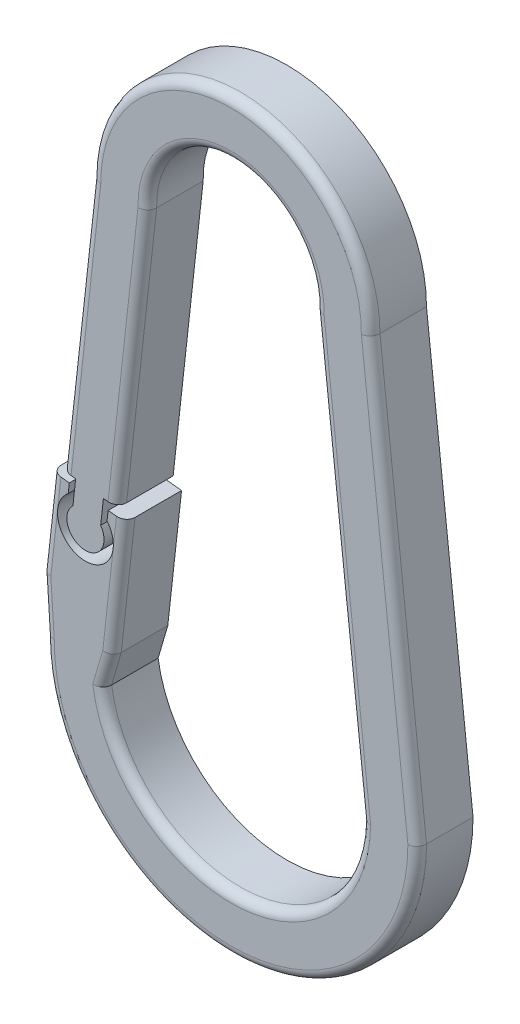
SolidWorks part; units mm, degrees
ref_plane "Спереди" through (0, 0, 0) normal (0, 0, 1) x (1, 0, 0)
ref_plane "Сверху" through (0, 0, 0) normal (0, 1, 0) x (1, 0, 0)
ref_plane "Справа" through (0, 0, 0) normal (1, 0, 0) x (0, 0, -1)
sketch "Эскиз1" plane through (0, 0, 0) normal (0, 0, 1) x (1, 0, 0)
  line L0 (-9.0941, 8.1534) -> (-7.5, 22.5)
  line L1 (10, 0) -> (7.5, 22.5)
  line L2 (0, 0) -> (0, 22.5) construction
  line L3 (6.9984, -0.1514) -> (4.4977, 22.3549)
  line L4 (-6.1124, 7.8221) -> (-4.4977, 22.3549)
  line L5 (-8.818, 6.1104) -> (-6.8302, 5.8896) construction
  line L6 (-7.0183, -0.3313) -> (-4.4977, 22.3549) construction
  line L7 (7.0183, -0.3313) -> (4.4977, 22.3549) construction
  line L8 (-7.8241, 6) -> (-7.6337, 7.7141) construction
  line L9 (-9.6352, 7.8111) -> (-8.691, 7.7062)
  line L10 (-8.4965, 6.7402) -> (-8.3487, 8.0706)
  line L11 (-7.0056, 6.5746) -> (-6.8578, 7.9049)
  line L12 (-8.3487, 8.0706) -> (-9.0941, 8.1534)
  line L13 (-6.8578, 7.9049) -> (-6.1124, 7.8221)
  line L14 (-10, 0) -> (-7.5, 22.5) construction
  line L15 (-8.691, 7.7062) -> (-8.7494, 7.1806)
  line L16 (-9.6352, 7.8111) -> (-10.1838, 2.8735)
  line L17 (-6.9192, -1.0602) -> (-6.3992, 0.7137)
  line L18 (-5.6596, 7.3694) -> (-6.3992, 0.7137)
  line L19 (-5.6596, 7.3694) -> (-6.6038, 7.4743)
  line L20 (-6.6038, 7.4743) -> (-6.6622, 6.9487)
  line L22 (-10, 0) -> (-10.1838, 2.8735)
  arc A0 (-10, 0) -> (10, 0) centre (0, 0) ccw
  arc A1 (7.5, 22.5) -> (-7.5, 22.5) centre (0, 22.5) ccw
  arc A2 (4.4977, 22.3549) -> (-4.4977, 22.3549) centre (0, 22.5) ccw
  arc A3 (-6.9192, -1.0602) -> (6.9984, -0.1514) centre (0, 0) ccw
  arc A4 (-8.4965, 6.7402) -> (-7.0056, 6.5746) centre (-7.8241, 6) ccw
  arc A5 (-9.2308, 3.8462) -> (9.2308, 3.8462) centre (0, 0) ccw construction
  arc A6 (-6.4615, 2.6923) -> (6.4615, 2.6923) centre (0, 0) ccw construction
  arc A7 (-8.7494, 7.1806) -> (-6.6622, 6.9487) centre (-7.8241, 6) ccw
  dimension "D1" = 20
  dimension "D2" = 15
  dimension "D3" = 40
  dimension "D5" = 2
  dimension "D8" = 6
  dimension "D9" = 3
  dimension "D13" = 170
  dimension "D6" = 1.5
  dimension "D7" = 2
  dimension "D10" = 0.4
  dimension "D11" = 0.3
  dimension "D12" = 0.5
  dimension "D14" = 170
  dimension "D15" = 0.5
  dimension "D4" = 3
extrude "Бобышка-Вытянуть1" add sketch "Эскиз1" along normal blind 3
fillet "Скругление2" radius 0.5 12 edges at (-10.0919, 1.4368, 3) (-9.9095, 5.3423, 3) (-6.0294, 4.0415, 3) (-6.6592, -0.1733, 3) (0.4561, -6.9851, 3) (5.748, 11.1017, 3) (0, 27, 3) (-5.305, 15.0885, 3) (-8.297, 15.3267, 3) (0, 30, 3) (8.75, 11.25, 3) (0, -10, 3)
